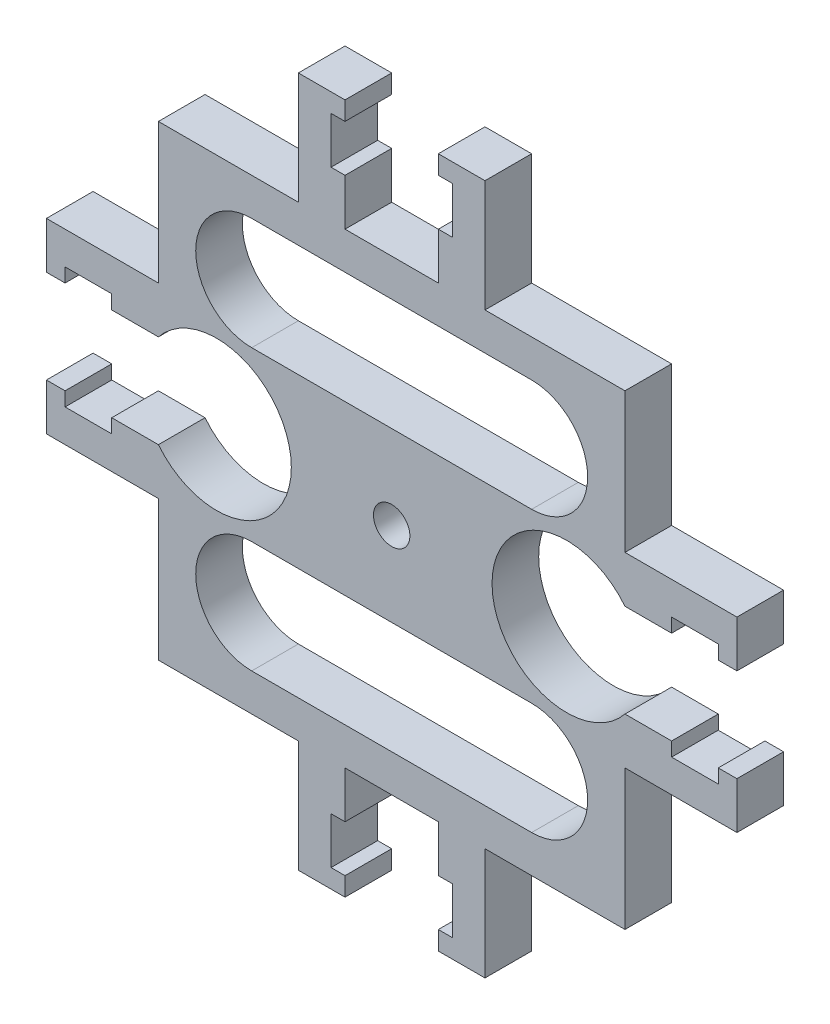
SolidWorks part; units mm, degrees
ref_plane "Plan de face" through (0, 0, 0) normal (0, 0, 1) x (1, 0, 0)
ref_plane "Plan de dessus" through (0, 0, 0) normal (0, 1, 0) x (1, 0, 0)
ref_plane "Plan de droite" through (0, 0, 0) normal (1, 0, 0) x (0, 0, -1)
sketch "Esquisse1" plane through (0, 0, 0) normal (0, 0, 1) x (1, 0, 0)
  line L0 (0, -10.9037) -> (0, 0) construction
  line L1 (0, 0) -> (78.1485, 0) construction
  line L2 (-25, 25) -> (-10, 25)
  line L3 (0, 0) -> (90.4553, 90.4553) construction
  line L4 (10, 25) -> (25, 25)
  line L5 (-25, -25) -> (-10, -25)
  line L6 (25, -25) -> (25, -10)
  line L8 (25, 10) -> (25, 25)
  line L9 (-25, -25) -> (-25, -10)
  line L10 (-25, 10) -> (-25, 25)
  line L11 (-15, 15) -> (15, 15) construction
  line L12 (-15, 21) -> (15, 21)
  line L13 (10, -25) -> (25, -25)
  line L14 (-15, 9) -> (15, 9)
  line L15 (-15, -15) -> (15, -15) construction
  line L16 (-15, -21) -> (15, -21)
  line L17 (-15, -9) -> (15, -9)
  line L18 (25, 5) -> (25, -5)
  line L19 (-25, 5) -> (-25, -5)
  circle A0 centre (0, 0) radius 1.95
  circle A1 centre (22, 0) radius 1.95 construction
  circle A2 centre (-22, 0) radius 1.95 construction
  arc A3 (-15, 21) -> (-15, 9) centre (-15, 15) ccw
  arc A4 (15, 9) -> (15, 21) centre (15, 15) ccw
  arc A5 (-15, -21) -> (-15, -9) centre (-15, -15) cw
  arc A6 (15, -9) -> (15, -21) centre (15, -15) cw
  arc A7 (25, 5) -> (25, -5) centre (18.755, 0) ccw
  arc A8 (-25, 5) -> (-25, -5) centre (-18.755, 0) cw
  point P20 (0, 15)
  point P32 (0, -15)
  line B0 (0, -25) -> (0, -13.135) construction
  line B1 (0, -25) -> (-5, -25)
  line B2 (-5, -30) -> (-10, -30) construction
  line B3 (-10, -30) -> (-10, -25)
  line B4 (-5, -30) -> (-5, -25)
  line B5 (0, -25) -> (5, -25)
  line B6 (5, -25) -> (5, -30)
  line B7 (5, -30) -> (10, -30) construction
  line B8 (10, -30) -> (10, -25)
  line B9 (-10, -30) -> (-10, -37)
  line B10 (-10, -37) -> (-5, -37)
  line B11 (-5, -37) -> (-5, -35)
  line B12 (-5, -35) -> (-6.5, -35)
  line B13 (-6.5, -35) -> (-6.5, -30)
  line B14 (-6.5, -30) -> (-5, -30)
  line B15 (5, -35) -> (6.5, -35)
  line B16 (10, -37) -> (5, -37)
  line B17 (5, -37) -> (5, -35)
  line B18 (6.5, -35) -> (6.5, -30)
  line B19 (10, -30) -> (10, -37)
  line B20 (10, -30) -> (10, -25)
  line B21 (5, -30) -> (6.5, -30)
  line B22 (0, -25) -> (0, -13.135) construction
  line B23 (0, -25) -> (5, -25)
  line B24 (5, -30) -> (10, -30) construction
  line B25 (10, -30) -> (10, -25)
  line B26 (5, -30) -> (5, -25)
  line B27 (0, -25) -> (-5, -25)
  line B28 (-5, -25) -> (-5, -30)
  line B29 (-5, -30) -> (-10, -30) construction
  line B30 (-10, -30) -> (-10, -25)
  line B31 (10, -30) -> (10, -37)
  line B32 (10, -37) -> (5, -37)
  line B33 (5, -37) -> (5, -35)
  line B34 (5, -35) -> (6.5, -35)
  line B35 (6.5, -35) -> (6.5, -30)
  line B36 (6.5, -30) -> (5, -30)
  line B37 (-5, -35) -> (-6.5, -35)
  line B38 (-10, -37) -> (-5, -37)
  line B39 (-5, -37) -> (-5, -35)
  line B40 (-6.5, -35) -> (-6.5, -30)
  line B41 (-10, -30) -> (-10, -37)
  line B42 (-10, -30) -> (-10, -25)
  line B43 (-5, -30) -> (-6.5, -30)
  line B44 (0, 25) -> (0, 13.135) construction
  line B45 (0, 25) -> (-5, 25)
  line B46 (-5, 30) -> (-10, 30) construction
  line B47 (-10, 30) -> (-10, 25)
  line B48 (-5, 30) -> (-5, 25)
  line B49 (0, 25) -> (5, 25)
  line B50 (5, 25) -> (5, 30)
  line B51 (5, 30) -> (10, 30) construction
  line B52 (10, 30) -> (10, 25)
  line B53 (-10, 30) -> (-10, 37)
  line B54 (-10, 37) -> (-5, 37)
  line B55 (-5, 37) -> (-5, 35)
  line B56 (-5, 35) -> (-6.5, 35)
  line B57 (-6.5, 35) -> (-6.5, 30)
  line B58 (-6.5, 30) -> (-5, 30)
  line B59 (5, 35) -> (6.5, 35)
  line B60 (10, 37) -> (5, 37)
  line B61 (5, 37) -> (5, 35)
  line B62 (6.5, 35) -> (6.5, 30)
  line B63 (10, 30) -> (10, 37)
  line B64 (10, 30) -> (10, 25)
  line B65 (5, 30) -> (6.5, 30)
  line B66 (25, 0) -> (13.135, 0) construction
  line B67 (25, 0) -> (25, -5)
  line B68 (30, -5) -> (30, -10) construction
  line B69 (30, -10) -> (25, -10)
  line B70 (30, -5) -> (25, -5)
  line B71 (25, 0) -> (25, 5)
  line B72 (25, 5) -> (30, 5)
  line B73 (30, 5) -> (30, 10) construction
  line B74 (30, 10) -> (25, 10)
  line B75 (30, -10) -> (37, -10)
  line B76 (37, -10) -> (37, -5)
  line B77 (37, -5) -> (35, -5)
  line B78 (35, -5) -> (35, -6.5)
  line B79 (35, -6.5) -> (30, -6.5)
  line B80 (30, -6.5) -> (30, -5)
  line B81 (35, 5) -> (35, 6.5)
  line B82 (37, 10) -> (37, 5)
  line B83 (37, 5) -> (35, 5)
  line B84 (35, 6.5) -> (30, 6.5)
  line B85 (30, 10) -> (37, 10)
  line B86 (30, 10) -> (25, 10)
  line B87 (30, 5) -> (30, 6.5)
  line B88 (-25, 0) -> (-13.135, 0) construction
  line B89 (-25, 0) -> (-25, -5)
  line B90 (-30, -5) -> (-30, -10) construction
  line B91 (-30, -10) -> (-25, -10)
  line B92 (-30, -5) -> (-25, -5)
  line B93 (-25, 0) -> (-25, 5)
  line B94 (-25, 5) -> (-30, 5)
  line B95 (-30, 5) -> (-30, 10) construction
  line B96 (-30, 10) -> (-25, 10)
  line B97 (-30, -10) -> (-37, -10)
  line B98 (-37, -10) -> (-37, -5)
  line B99 (-37, -5) -> (-35, -5)
  line B100 (-35, -5) -> (-35, -6.5)
  line B101 (-35, -6.5) -> (-30, -6.5)
  line B102 (-30, -6.5) -> (-30, -5)
  line B103 (-35, 5) -> (-35, 6.5)
  line B104 (-37, 10) -> (-37, 5)
  line B105 (-37, 5) -> (-35, 5)
  line B106 (-35, 6.5) -> (-30, 6.5)
  line B107 (-30, 10) -> (-37, 10)
  line B108 (-30, 10) -> (-25, 10)
  line B109 (-30, 5) -> (-30, 6.5)
  dimension "D11" = 3.9
  dimension "D4" = 3.9
  dimension "D8" = 6
  dimension "D9" = 8
  dimension "D2" = 50
  dimension "D3" = 50
  dimension "D5" = 45
  dimension "D6" = 22
  dimension "D7" = 10
sketch_block_instance "Insert plots ep 5mm avec ergots-1"
sketch_block "Insert plots ep 5mm avec ergots" parameters "D1"=10, "D2"=5, "D3"=5, "D4"=5, "D5"=2, "D6"=1.5, "D7"=2, "D8"=2, "D9"=2.0716, "D10"=2
sketch_block_instance "Insert plots ep 5mm avec ergots-3"
sketch_block_instance "Insert plots ep 5mm avec ergots-4"
sketch_block_instance "Insert plots ep 5mm avec ergots-6"
sketch_block_instance "Insert plots ep 5mm avec ergots-7"
extrude "Boss.-Extru.1" add sketch "Esquisse1" along normal blind 5 contours L4 B52 B63 B60 B61 B59 B62 B65 B50 B49 region at (-17.5, 23.9535, 0)
